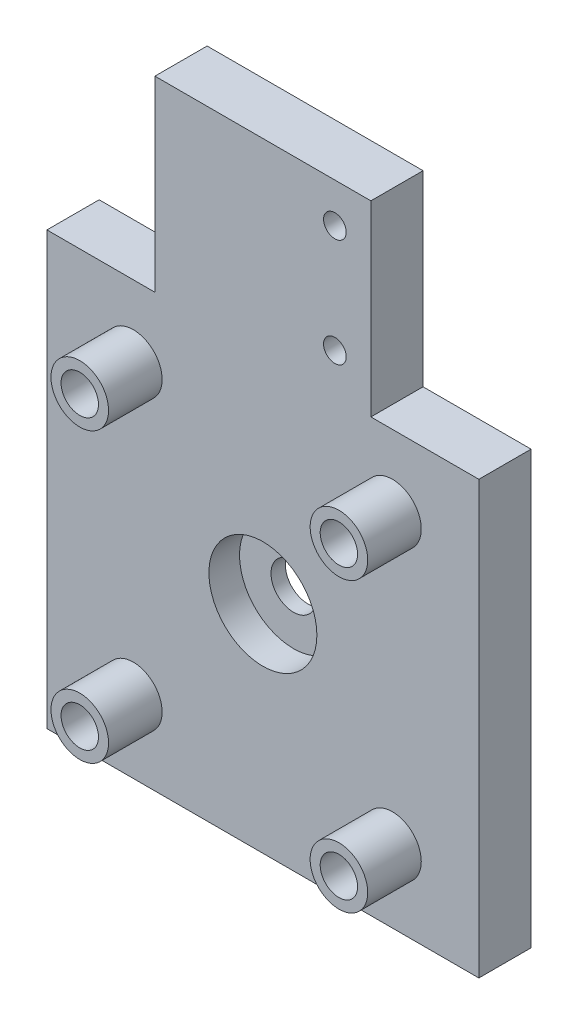
SolidWorks part; units mm, degrees
ref_plane "Front Plane" through (0, 0, 0) normal (0, 0, 1) x (1, 0, 0)
ref_plane "Top Plane" through (0, 0, 0) normal (0, 1, 0) x (1, 0, 0)
ref_plane "Right Plane" through (0, 0, 0) normal (1, 0, 0) x (0, 0, -1)
sketch "Sketch1" plane through (0, 0, 0) normal (0, 0, 1) x (1, 0, 0)
  line L1 (-19.05, -38.1) -> (19.05, -38.1)
  line L2 (-19.05, -38.1) -> (-19.05, 38.1)
  line L3 (-19.05, 38.1) -> (19.05, 38.1)
  line L4 (19.05, -38.1) -> (19.05, 38.1)
  line L5 (-19.05, -38.1) -> (19.05, 38.1) construction
  line L6 (-19.05, 38.1) -> (19.05, -38.1) construction
  point P0 (0, 0)
  dimension "D1" = 38.1
  dimension "D2" = 76.2
extrude "Boss-Extrude1" add sketch "Sketch1" along normal blind 7.9375
sketch "Sketch2" plane through (0, 0, 7.9375) normal (0, 0, 1) x (1, 0, 0)
  circle A0 centre (0, 0) radius 3.9688
  dimension "D1" = 7.9375
extrude "Cut-Extrude1" cut sketch "Sketch2" against normal through all
sketch "Sketch4" plane through (0, 0, 7.9375) normal (0, 0, 1) x (1, 0, 0)
  circle A0 centre (0, 0) radius 9.525
  dimension "D1" = 19.05
extrude "Cut-Extrude2" cut sketch "Sketch4" against normal offset from surface (5.3975 mm away) 2.54 up to face at (3.9688, 0, 0)
sketch "Sketch8" plane through (0, 0, 7.9375) normal (0, 0, 1) x (1, 0, 0)
  line L0 (-19.05, -38.1) -> (19.05, -38.1) construction
  line L1 (-19.05, 38.1) -> (-38.1, 38.1)
  line L2 (-19.05, 38.1) -> (-19.05, -38.1)
  line L3 (-19.05, -38.1) -> (-38.1, -38.1)
  line L4 (-38.1, 38.1) -> (-38.1, -38.1)
  line L5 (0, 38.1) -> (0, -38.1) construction
  line L6 (19.05, 38.1) -> (-19.05, 38.1) construction
  line L7 (19.05, -38.1) -> (38.1, -38.1)
  line L8 (38.1, 38.1) -> (38.1, -38.1)
  line L9 (19.05, 38.1) -> (38.1, 38.1)
  line L10 (19.05, 38.1) -> (19.05, -38.1)
  dimension "D1" = 38.1
extrude "Boss-Extrude5" add sketch "Sketch8" against normal up to surface (7.9375 mm away) up to face at (3.9688, 0, 0)
sketch "Sketch5" plane through (0, 0, 7.9375) normal (0, 0, 1) x (1, 0, 0)
  line L0 (38.1, 38.1) -> (-38.1, 38.1) construction
  line L1 (0, 38.1) -> (0, -38.1) construction
  line L2 (38.1, 38.1) -> (-38.1, 38.1) construction
  line L3 (-38.1, -38.1) -> (38.1, -38.1) construction
  circle A0 centre (22.86, 25.4) radius 5.08
  circle A1 centre (-22.86, 25.4) radius 5.08
  dimension "D1" = 10.16
  dimension "D2" = 12.7
  dimension "D3" = 22.86
extrude "Boss-Extrude2" add sketch "Sketch5" along normal blind 9.4488
sketch "Sketch6" plane through (0, 0, 17.3863) normal (0, 0, 1) x (1, 0, 0)
  line L0 (0, 38.1) -> (0, -38.1) construction
  line L1 (38.1, 38.1) -> (-38.1, 38.1) construction
  line L2 (-38.1, -38.1) -> (38.1, -38.1) construction
  circle A0 centre (22.86, 25.4) radius 3.302
  circle A1 centre (-22.86, 25.4) radius 3.302
  dimension "D1" = 6.604
extrude "Cut-Extrude3" cut sketch "Sketch6" against normal through all
mirror "Mirror1" about plane through (0, 0, 0) normal (0, 1, 0) of "Cut-Extrude3", "Boss-Extrude2"
sketch "Sketch7" plane through (0, 0, 7.9375) normal (0, 0, 1) x (1, 0, 0)
  line L1 (-19.05, 38.1) -> (19.05, 38.1)
  line L2 (-19.05, 38.1) -> (-19.05, 71.12)
  line L3 (-19.05, 71.12) -> (19.05, 71.12)
  line L4 (19.05, 38.1) -> (19.05, 71.12)
  line L5 (-19.05, 54.61) -> (19.05, 54.61) construction
  line L6 (12.7, 71.12) -> (12.7, 38.1) construction
  line L7 (38.1, 38.1) -> (-38.1, 38.1) construction
  line L8 (0, 71.12) -> (0, -38.1) construction
  line L9 (-38.1, -38.1) -> (38.1, -38.1) construction
  circle A0 centre (12.7, 64.135) radius 2
  circle A1 centre (12.7, 45.085) radius 2
  dimension "D4" = 4
  dimension "D1" = 33.02
  dimension "D2" = 9.525
  dimension "D3" = 6.35
  dimension "D5" = 38.1
extrude "Boss-Extrude4" add sketch "Sketch7" against normal up to surface (7.9375 mm away) up to face at (26.162, -25.4, 0)
sketch "Sketch9" plane through (0, 0, 0) normal (0, 0, -1) x (-1, 0, 0)
  line L1 (-12.7, -12.7) -> (12.7, -12.7)
  line L2 (-12.7, -12.7) -> (-12.7, 12.7)
  line L3 (-12.7, 12.7) -> (12.7, 12.7)
  line L4 (12.7, -12.7) -> (12.7, 12.7)
  line L5 (-12.7, -12.7) -> (12.7, 12.7) construction
  line L6 (-12.7, 12.7) -> (12.7, -12.7) construction
  line L14 (-19.05, 38.1) -> (-38.1, 38.1)
  line L15 (-38.1, 38.1) -> (-38.1, -38.1)
  line L16 (-38.1, -38.1) -> (38.1, -38.1)
  line L17 (38.1, -38.1) -> (38.1, 38.1)
  line L18 (38.1, 38.1) -> (19.05, 38.1)
  line L19 (19.05, 38.1) -> (19.05, 71.12)
  line L20 (19.05, 71.12) -> (-19.05, 71.12)
  line L21 (-19.05, 71.12) -> (-19.05, 38.1)
  line L22 (-19.05, 38.1) -> (-38.1, 38.1)
  line L23 (-38.1, 38.1) -> (-38.1, -38.1)
  line L24 (-38.1, -38.1) -> (38.1, -38.1)
  line L25 (38.1, -38.1) -> (38.1, 38.1)
  line L26 (38.1, 38.1) -> (19.05, 38.1)
  line L27 (19.05, 38.1) -> (19.05, 71.12)
  line L28 (19.05, 71.12) -> (-19.05, 71.12)
  line L29 (-19.05, 71.12) -> (-19.05, 38.1)
  circle A1 centre (22.86, 25.4) radius 3.302
  circle A2 centre (22.86, 25.4) radius 3.302
  circle A3 centre (-22.86, 25.4) radius 3.302
  circle A4 centre (-22.86, 25.4) radius 3.302
  circle A5 centre (22.86, -25.4) radius 3.302
  circle A6 centre (22.86, -25.4) radius 3.302
  circle A7 centre (-22.86, -25.4) radius 3.302
  circle A8 centre (-22.86, -25.4) radius 3.302
  circle A9 centre (-12.7, 45.085) radius 2
  circle A10 centre (-12.7, 45.085) radius 2
  circle A11 centre (-12.7, 64.135) radius 2
  circle A12 centre (-12.7, 64.135) radius 2
  point P0 (0, 0)
  point P24 (0, 0)
  point P27 (0, 0)
  dimension "D7" = 25.4
  dimension "D8" = 25.4
  dimension "D1" = 0
  dimension "D2" = 0
  dimension "D3" = 0
  dimension "D4" = 0
  dimension "D5" = 0
  dimension "D6" = 0
  dimension "D9" = 0
extrude "Boss-Extrude6" add sketch "Sketch9" along normal blind 1.27 contours L22 L23 L24 L25 L26 L27 L28 L29 | A10 | A12 | A4 | L2 L1 L4 L3 | A8 | A6 | A2
